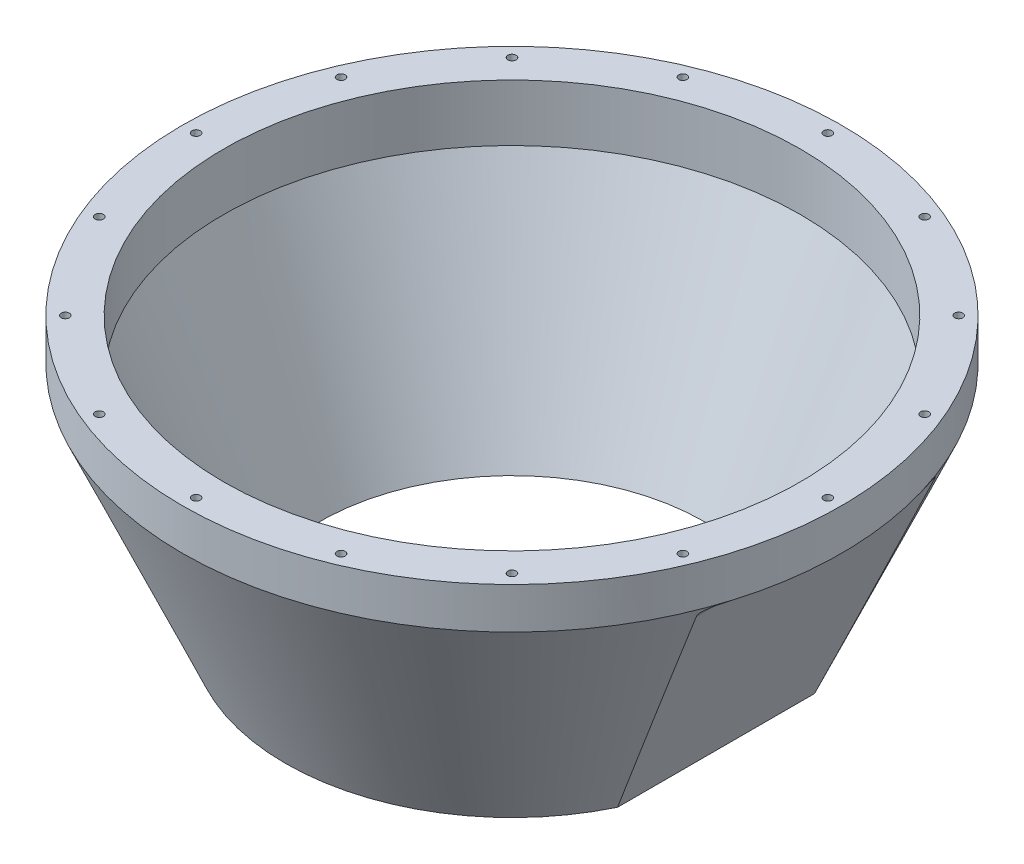
SolidWorks part; units mm, degrees
material "6061-T6 (SS)"
ref_plane "Front Plane" through (0, 0, 0) normal (0, 0, 1) x (1, 0, 0)
ref_plane "Top Plane" through (0, 0, 0) normal (0, 1, 0) x (1, 0, 0)
ref_plane "Right Plane" through (0, 0, 0) normal (1, 0, 0) x (0, 0, -1)
sketch "Sketch1" plane through (0, 0, 0) normal (0, 1, 0) x (1, 0, 0)
  circle A0 centre (0, 0) radius 152.4
  circle A1 centre (0, 0) radius 88.9
  dimension "D1" = 304.8
  dimension "D2" = 177.8
extrude "Boss-Extrude1" add sketch "Sketch1" along normal blind 127
sketch "Sketch2" plane through (0, 0, 0) normal (0, 0, 1) x (1, 0, 0)
  line L0 (152.4, 107.95) -> (104.775, 0)
  line L1 (152.4, 0) -> (152.4, 127) construction
  line L2 (-152.4, 0) -> (152.4, 0) construction
  line L3 (104.775, 0) -> (152.4, 0)
  line L4 (152.4, 0) -> (152.4, 107.95)
  line L5 (152.4, 127) -> (-152.4, 127) construction
  point P13 (0, 0)
  dimension "D1" = 104.775
  dimension "D2" = 19.05
revolve "Cut-Revolve1" cut sketch "Sketch2" angle 360 about axis through (0, 127, 0) along (0, -1, 0)
sketch "Sketch3" plane through (0, 0, 0) normal (0, 0, 1) x (1, 0, 0)
  line L0 (141.9892, 107.95) -> (94.3642, 0)
  line L1 (152.4, 107.95) -> (141.9892, 107.95)
  line L2 (152.4, 107.95) -> (104.775, 0)
  line L3 (104.775, 0) -> (94.3642, 0)
  line L6 (-88.9, 0) -> (88.9, 0) construction
  line L8 (152.4, 107.95) -> (-152.4, 107.95) construction
  point P3 (139.8155, 79.7974)
  dimension "D1" = 9.525
extrude "Cut-Extrude1" cut sketch "Sketch3" against normal through all both and the other way through all
mirror "Mirror1" about plane through (0, 0, 0) normal (1, 0, 0) of "Cut-Extrude1"
fillet "Fillet1" radius 6.35 2 edges at (-141.9892, 107.95, 0) (141.9892, 107.95, 0)
sketch "Sketch4" plane through (0, 0, 0) normal (0, 0, 1) x (1, 0, 0)
  line L0 (133.35, 100.7533) -> (88.9, 0)
  line L2 (-94.3642, 0) -> (94.3642, 0) construction
  line L3 (88.9, 0) -> (0, 0)
  line L4 (0, 0) -> (0, 127)
  line L6 (94.3642, 0) -> (140.3185, 104.1631) construction
  line L10 (133.35, 100.7533) -> (133.35, 127)
  line L11 (133.35, 127) -> (0, 127)
  line L13 (152.4, 127) -> (-152.4, 127) construction
  point P2 (0, 0)
  dimension "D1" = 88.9
  dimension "D2" = 133.35
revolve "Cut-Revolve2" cut sketch "Sketch4" angle 360 about L4
hole_wizard "#10-24 Tapped Hole1" positions "Sketch5" profile "Sketch7" tap size "#10-24" standard "ANSI Inch"
sketch "Sketch5" plane through (0, 127, 0) normal (0, 1, 0) x (1, 0, 0)
  line L0 (0, 0) -> (146.05, 0) construction
  point P0 (146.05, 0)
  dimension "D1" = 146.05
cosmetic thread "Hole Thread1" parameters "D1"=9.652, "D2"=4.826
sketch "Sketch7" plane through (146.05, 127, 0) normal (1, 0, 0) x (0, 0, 1)
  line L0 (0, 0) -> (0, 14.0948)
  line L1 (0, 14.0948) -> (1.8986, 12.954)
  line L2 (1.8986, 12.954) -> (1.8986, 0)
  line L5 (1.8986, 0) -> (0, 0)
  line L10 (0, 14.0948) -> (-1.8987, 12.954) construction
  line L11 (0, -6.35) -> (0, 107.95) construction
  dimension "Tap Drill Dia." = 3.7973
  dimension "Tap Drill Depth" = 12.954
  dimension "Drill Angle" = 118
pattern_circular "CirPattern1" count 16 over 360 about axis through (0, 127, 0) along (0, 1, 0) of "#10-24 Tapped Hole1"
